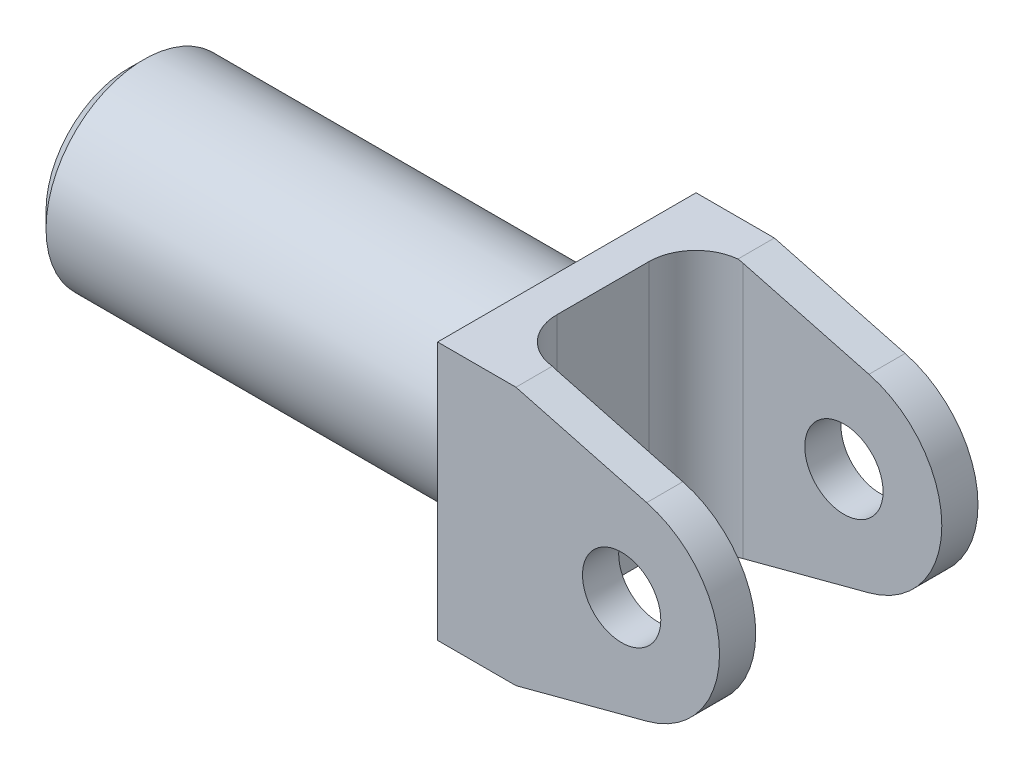
SolidWorks part; units mm, degrees
material "Alloy Steel"
ref_plane "Front Plane" through (0, 0, 0) normal (0, 0, 1) x (1, 0, 0)
ref_plane "Top Plane" through (0, 0, 0) normal (0, 1, 0) x (1, 0, 0)
ref_plane "Right Plane" through (0, 0, 0) normal (1, 0, 0) x (0, 0, -1)
sketch "Sketch1" plane through (0, 0, 0) normal (0, 1, 0) x (1, 0, 0)
  line L2 (0, -10.4775) -> (22.86, -10.4775)
  line L3 (0, -10.4775) -> (0, 10.4775)
  line L4 (0, 10.4775) -> (22.86, 10.4775)
  line L5 (22.86, -10.4775) -> (22.86, 10.4775)
  point P0 (0, 0)
  dimension "D1" = 20.955
  dimension "D2" = 22.86
extrude "Boss-Extrude1" add sketch "Sketch1" along normal mid plane 20.955
sketch "Sketch2" plane through (0, 10.4775, 0) normal (0, 1, 0) x (1, 0, 0)
  line L0 (-37.6496, 0) -> (34.9985, 0) construction
  line L1 (2.921, -3.7338) -> (2.921, 3.7338)
  line L2 (6.731, 7.5438) -> (22.86, 7.5438)
  line L3 (22.86, -10.4775) -> (22.86, 10.4775) construction
  line L4 (6.731, -7.5438) -> (22.86, -7.5438)
  arc A0 (6.731, 7.5438) -> (2.921, 3.7338) centre (6.731, 3.7338) ccw
  arc A1 (6.731, -7.5438) -> (2.921, -3.7338) centre (6.731, -3.7338) cw
  point P10 (2.921, 7.5438)
  point P12 (2.921, 0)
  dimension "D3" = 3.81
  dimension "D1" = 7.5438
  dimension "D2" = 19.939
extrude "Cut-Extrude1" cut sketch "Sketch2" against normal through all and the other way through all
sketch "Sketch3" plane through (0, 0, 10.4775) normal (0, 0, 1) x (1, 0, 0)
  line L0 (-38.5706, 0) -> (33.6293, 0) construction
  line L1 (22.86, 10.4775) -> (22.86, -10.4775) construction
  line L2 (6.35, 10.4775) -> (16.9519, 7.6737)
  line L3 (0, 10.4775) -> (22.86, 10.4775) construction
  line L4 (6.35, -10.4775) -> (16.9519, -7.6737)
  circle A0 centre (14.9225, 0) radius 3.175
  arc A1 (16.9519, -7.6737) -> (16.9519, 7.6737) centre (14.9225, 0) ccw
  line M1 (0, -10.4775) -> (22.86, -10.4775)
  line M2 (22.86, -10.4775) -> (22.86, 10.4775)
  line M3 (22.86, 10.4775) -> (0, 10.4775)
  dimension "D1" = 6.35
  dimension "D2" = 15.875
  dimension "D3" = 6.35
extrude "Cut-Extrude2" cut sketch "Sketch3" against normal through all contours A1 L2 M2 M3 | A1 L4 M1 M2 | A0 L0 | L0 A0 region at (14.9225, 1.3475, 10.4775) region at (18.0582, 8.3763, 10.4775) region at (18.0582, -8.3763, 10.4775) region at (14.9225, -1.3475, 10.4775)
sketch "Sketch4" plane through (0, 0, 0) normal (-1, 0, 0) x (0, 0, 1)
  circle A0 centre (0, 0) radius 7.9375
  dimension "D1" = 15.875
extrude "Boss-Extrude2" add sketch "Sketch4" along normal blind 35.56
sketch "Sketch5" plane through (-35.56, 0, 0) normal (-1, 0, 0) x (0, 0, 1)
  circle A0 centre (0, 0) radius 4.7625
  dimension "D1" = 9.525
extrude "Cut-Extrude3" cut sketch "Sketch5" against normal blind 31.242
fillet "Fillet1" radius 2.54 1 edges at (0, 0, -7.9375)
chamfer "Chamfer1" distance 1.27 angle 45 1 edges at (-35.56, 0, 7.9375)
sketch3d "3DSketch1"
  line L0 (14.9225, 0, 10.4775) -> (14.9225, 0, -10.4775) construction
  line L1 (14.9225, 0, 7.5438) -> (14.9225, 0, 10.4775) construction
  line L2 (14.9225, 0, 7.5438) -> (14.9225, 0, 10.4775) construction
  line L3 (14.9225, 0, -10.4775) -> (14.9225, 0, -7.5438) construction
  point P8 (14.9225, 0, 0)
